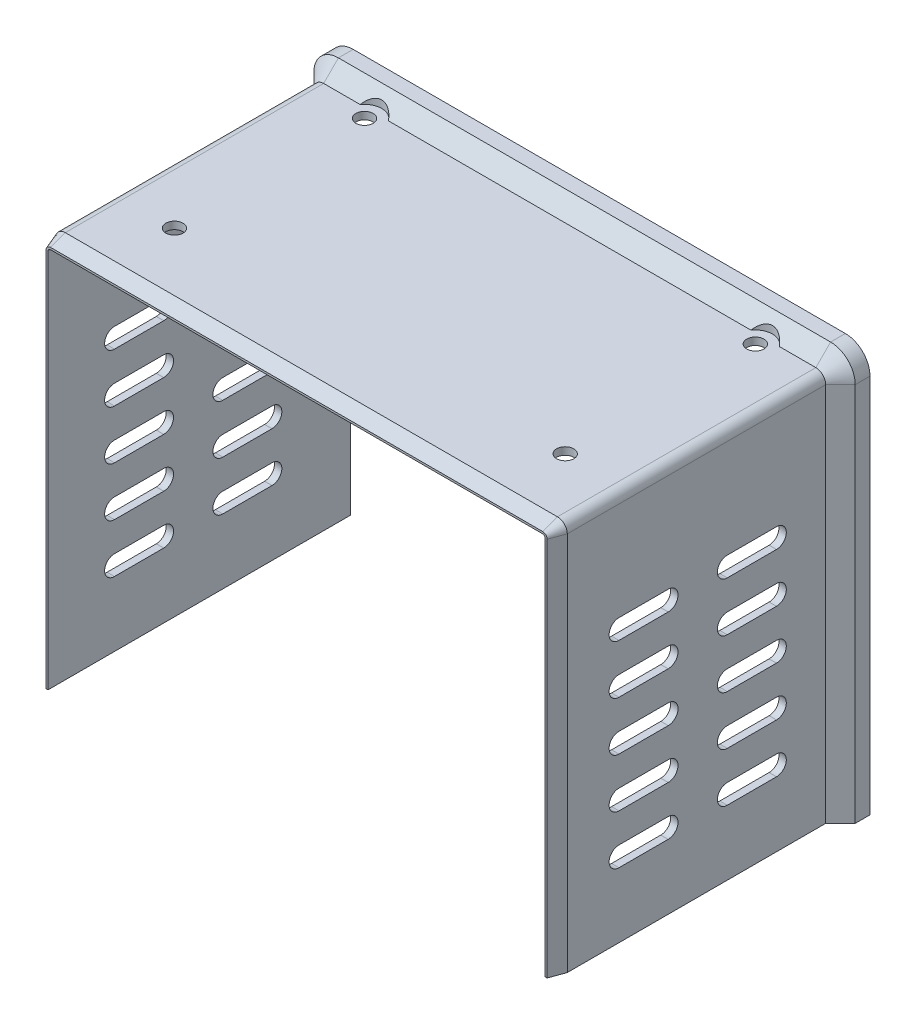
SolidWorks part; units mm, degrees
ref_plane "Front Plane" through (0, 0, 0) normal (0, 0, 1) x (1, 0, 0)
ref_plane "Top Plane" through (0, 0, 0) normal (0, 1, 0) x (1, 0, 0)
ref_plane "Right Plane" through (0, 0, 0) normal (1, 0, 0) x (0, 0, -1)
sketch "Sketch3" plane through (0, 0, 389.6201) normal (0, 0, 1) x (1, 0, 0)
  line L0 (-161.2108, -568.2989) -> (-161.2108, -472.2989) construction
  line L1 (-161.2108, -470.0989) -> (-61.2108, -470.0989)
  line L2 (-161.7108, -470.5989) -> (-161.7108, -544.9977)
  line L4 (-60.7108, -470.5989) -> (-60.7108, -547.7989)
  line L5 (-61.2108, -472.2989) -> (-61.2108, -568.2989) construction
  line L6 (-159.2108, -470.2989) -> (-118.3071, -470.2989) construction
  line L7 (-163.2108, -470.5989) -> (-163.2108, -547.7989)
  line L8 (-161.2108, -468.5989) -> (-61.2108, -468.5989)
  line L9 (-59.2108, -470.5989) -> (-59.2108, -547.7989)
  line L10 (-163.2108, -547.7989) -> (-161.7108, -547.7989)
  line L11 (-59.2108, -547.7989) -> (-60.7108, -547.7989)
  line L12 (-161.7108, -470.0989) -> (-60.7108, -470.0989) construction
  line L13 (-161.7108, -470.0989) -> (-161.7108, -547.7989) construction
  line L14 (-163.2108, -468.5989) -> (-59.2108, -468.5989) construction
  line L15 (-163.2108, -468.5989) -> (-163.2108, -547.7989) construction
  line L16 (-59.2108, -468.5989) -> (-59.2108, -547.7989) construction
  line L17 (-60.7108, -470.0989) -> (-60.7108, -547.7989) construction
  line L18 (-161.7108, -544.9977) -> (-161.7108, -547.7989)
  line L19 (-175.2108, -548.2989) -> (-161.8182, -548.2989) construction
  line L20 (-60.2182, -548.2989) -> (-47.2108, -548.2989) construction
  arc A1 (-161.2108, -470.0989) -> (-161.7108, -470.5989) centre (-161.2108, -470.5989) ccw
  arc A3 (-161.2108, -468.5989) -> (-163.2108, -470.5989) centre (-161.2108, -470.5989) ccw
  arc A4 (-59.2108, -470.5989) -> (-61.2108, -468.5989) centre (-61.2108, -470.5989) ccw
  arc A5 (-60.7108, -470.5989) -> (-61.2108, -470.0989) centre (-61.2108, -470.5989) ccw
  dimension "D5" = 0.5
  dimension "D6" = 2
  dimension "D7" = 2
  dimension "D8" = 0.5
  dimension "D1" = 0.5
  dimension "D2" = 0.5
  dimension "D3" = 0.2
  dimension "D9" = 0.5
  dimension "D10" = 0.5
  dimension "D4" = 1.5
extrude "Boss-Extrude1" add sketch "Sketch3" along normal blind 61.5
chamfer "Chamfer1" distance 3 angle 20 5 edges at (-59.2108, -509.1989, 451.1201) (-163.2108, -509.1989, 451.1201) (-59.7966, -469.1847, 451.1201) (-162.6251, -469.1847, 451.1201) (-111.2108, -468.5989, 451.1201) first distance on face at (-59.2108, -509.1989, 420.3701) first distance on face at (-163.2108, -509.1989, 420.3701) first distance on face at (-60.0037, -469.3918, 420.3701) first distance on face at (-162.418, -469.3918, 420.3701) first distance on face at (-111.2108, -468.5989, 420.3701)
sketch "Sketch4" plane through (0, -468.5989, 0) normal (0, 1, 0) x (1, 0, 0)
  line L0 (-163.2108, -448.1201) -> (-163.2108, -389.6201) construction
  line L1 (-61.2108, -389.6201) -> (-161.2108, -389.6201) construction
  line L2 (-111.2108, -389.6201) -> (-111.2108, -452.2414) construction
  line L3 (-61.2108, -452.2414) -> (-161.2108, -452.2414) construction
  line L5 (-59.2108, -448.1201) -> (-59.2108, -389.6201) construction
  circle A0 centre (-150.9108, -397.6201) radius 1.75
  circle A1 centre (-71.5108, -397.6201) radius 1.75
  circle A2 centre (-71.5108, -436.2414) radius 1.75
  circle A3 centre (-150.9108, -436.2414) radius 1.75
  dimension "D1" = 12.3
  dimension "D2" = 8
  dimension "D3" = 3.5
  dimension "D5" = 16
  dimension "D6" = 12.3
  dimension "D7" = 12.3
  dimension "D4" = 16
extrude "Cut-Extrude1" cut sketch "Sketch4" against normal blind 10
sketch "Sketch5" plane through (0, 0, 389.6201) normal (0, 0, -1) x (-1, 0, 0)
  line L9 (59.3108, -547.7989) -> (59.3108, -470.5989)
  line L10 (61.2108, -468.6989) -> (161.2108, -468.6989)
  line L11 (163.1108, -470.5989) -> (163.1108, -547.7989)
  line L12 (166.2108, -470.5989) -> (166.2108, -547.7989)
  line L13 (61.2108, -465.5989) -> (161.2108, -465.5989)
  line L14 (56.2108, -547.7989) -> (56.2108, -470.5989)
  line L15 (166.2108, -470.5989) -> (166.2108, -547.7989)
  line L16 (61.2108, -465.5989) -> (161.2108, -465.5989)
  line L17 (56.2108, -547.7989) -> (56.2108, -470.5989)
  line L18 (56.2108, -547.7989) -> (59.3108, -547.7989)
  line L19 (163.1108, -547.7989) -> (166.2108, -547.7989)
  arc A6 (61.2108, -468.6989) -> (59.3108, -470.5989) centre (61.2108, -470.5989) ccw
  arc A7 (163.1108, -470.5989) -> (161.2108, -468.6989) centre (161.2108, -470.5989) ccw
  arc A8 (166.2108, -470.5989) -> (161.2108, -465.5989) centre (161.2108, -470.5989) ccw
  arc A9 (61.2108, -465.5989) -> (56.2108, -470.5989) centre (61.2108, -470.5989) ccw
  arc A10 (166.2108, -470.5989) -> (161.2108, -465.5989) centre (161.2108, -470.5989) ccw
  arc A11 (61.2108, -465.5989) -> (56.2108, -470.5989) centre (61.2108, -470.5989) ccw
  dimension "D1" = 3
  dimension "D2" = 3.1
extrude "Boss-Extrude2" add sketch "Sketch5" against normal blind 3
chamfer "Chamfer2" distance 3 angle 45 5 edges at (-163.2108, -509.1989, 392.6201) (-162.6251, -469.1847, 392.6201) (-111.2108, -468.5989, 392.6201) (-59.7966, -469.1847, 392.6201) (-59.2108, -509.1989, 392.6201)
sketch "Sketch6" plane through (-59.2108, 0, 0) normal (1, 0, 0) x (0, 0, -1)
  line L0 (-437.6201, -492.5989) -> (-427.6201, -492.5989) construction
  line L1 (-437.6201, -490.5989) -> (-427.6201, -490.5989)
  line L2 (-437.6201, -494.5989) -> (-427.6201, -494.5989)
  line L3 (-448.1201, -470.5989) -> (-448.1201, -547.7989) construction
  line L4 (-448.1201, -470.5989) -> (-395.6201, -470.5989) construction
  line L5 (-415.6201, -492.5989) -> (-405.6201, -492.5989) construction
  line L6 (-415.6201, -490.5989) -> (-405.6201, -490.5989)
  line L7 (-415.6201, -494.5989) -> (-405.6201, -494.5989)
  line L8 (-437.6201, -522.5989) -> (-427.6201, -522.5989) construction
  line L9 (-437.6201, -502.5989) -> (-427.6201, -502.5989) construction
  line L10 (-437.6201, -500.5989) -> (-427.6201, -500.5989)
  line L11 (-437.6201, -504.5989) -> (-427.6201, -504.5989)
  line L12 (-415.6201, -502.5989) -> (-405.6201, -502.5989) construction
  line L13 (-415.6201, -500.5989) -> (-405.6201, -500.5989)
  line L14 (-415.6201, -504.5989) -> (-405.6201, -504.5989)
  line L15 (-437.6201, -512.5989) -> (-427.6201, -512.5989) construction
  line L16 (-437.6201, -510.5989) -> (-427.6201, -510.5989)
  line L17 (-437.6201, -514.5989) -> (-427.6201, -514.5989)
  line L18 (-415.6201, -512.5989) -> (-405.6201, -512.5989) construction
  line L19 (-415.6201, -510.5989) -> (-405.6201, -510.5989)
  line L20 (-415.6201, -514.5989) -> (-405.6201, -514.5989)
  line L21 (-437.6201, -520.5989) -> (-427.6201, -520.5989)
  line L22 (-437.6201, -524.5989) -> (-427.6201, -524.5989)
  line L23 (-415.6201, -522.5989) -> (-405.6201, -522.5989) construction
  line L24 (-415.6201, -520.5989) -> (-405.6201, -520.5989)
  line L25 (-415.6201, -524.5989) -> (-405.6201, -524.5989)
  line L26 (-437.6201, -532.5989) -> (-427.6201, -532.5989) construction
  line L27 (-437.6201, -530.5989) -> (-427.6201, -530.5989)
  line L28 (-437.6201, -534.5989) -> (-427.6201, -534.5989)
  line L29 (-415.6201, -532.5989) -> (-405.6201, -532.5989) construction
  line L30 (-415.6201, -530.5989) -> (-405.6201, -530.5989)
  line L31 (-415.6201, -534.5989) -> (-405.6201, -534.5989)
  arc A0 (-437.6201, -490.5989) -> (-437.6201, -494.5989) centre (-437.6201, -492.5989) ccw
  arc A1 (-427.6201, -494.5989) -> (-427.6201, -490.5989) centre (-427.6201, -492.5989) ccw
  arc A2 (-415.6201, -490.5989) -> (-415.6201, -494.5989) centre (-415.6201, -492.5989) ccw
  arc A3 (-405.6201, -494.5989) -> (-405.6201, -490.5989) centre (-405.6201, -492.5989) ccw
  arc A4 (-437.6201, -500.5989) -> (-437.6201, -504.5989) centre (-437.6201, -502.5989) ccw
  arc A5 (-427.6201, -504.5989) -> (-427.6201, -500.5989) centre (-427.6201, -502.5989) ccw
  arc A6 (-415.6201, -500.5989) -> (-415.6201, -504.5989) centre (-415.6201, -502.5989) ccw
  arc A7 (-405.6201, -504.5989) -> (-405.6201, -500.5989) centre (-405.6201, -502.5989) ccw
  arc A8 (-437.6201, -510.5989) -> (-437.6201, -514.5989) centre (-437.6201, -512.5989) ccw
  arc A9 (-427.6201, -514.5989) -> (-427.6201, -510.5989) centre (-427.6201, -512.5989) ccw
  arc A10 (-415.6201, -510.5989) -> (-415.6201, -514.5989) centre (-415.6201, -512.5989) ccw
  arc A11 (-405.6201, -514.5989) -> (-405.6201, -510.5989) centre (-405.6201, -512.5989) ccw
  arc A12 (-437.6201, -520.5989) -> (-437.6201, -524.5989) centre (-437.6201, -522.5989) ccw
  arc A13 (-427.6201, -524.5989) -> (-427.6201, -520.5989) centre (-427.6201, -522.5989) ccw
  arc A14 (-415.6201, -520.5989) -> (-415.6201, -524.5989) centre (-415.6201, -522.5989) ccw
  arc A15 (-405.6201, -524.5989) -> (-405.6201, -520.5989) centre (-405.6201, -522.5989) ccw
  arc A16 (-437.6201, -530.5989) -> (-437.6201, -534.5989) centre (-437.6201, -532.5989) ccw
  arc A17 (-427.6201, -534.5989) -> (-427.6201, -530.5989) centre (-427.6201, -532.5989) ccw
  arc A18 (-415.6201, -530.5989) -> (-415.6201, -534.5989) centre (-415.6201, -532.5989) ccw
  arc A19 (-405.6201, -534.5989) -> (-405.6201, -530.5989) centre (-405.6201, -532.5989) ccw
  point P2 (-432.6201, -492.5989)
  point P14 (-410.6201, -492.5989)
  point P22 (-432.6201, -502.5989)
  point P29 (-410.6201, -502.5989)
  point P36 (-432.6201, -512.5989)
  point P43 (-410.6201, -512.5989)
  point P48 (-432.6201, -522.5989)
  point P55 (-410.6201, -522.5989)
  point P62 (-432.6201, -532.5989)
  point P69 (-410.6201, -532.5989)
  dimension "D1" = 2
  dimension "D2" = 10
  dimension "D3" = 10.5
  dimension "D4" = 20
  dimension "D6" = 5
  dimension "D5" = 2
extrude "Cut-Extrude2" cut sketch "Sketch6" against normal blind 145
sketch "Sketch7" plane through (0, -468.5989, 0) normal (0, 1, 0) x (1, 0, 0)
  circle A0 centre (-150.9108, -397.6201) radius 3.5
  circle A1 centre (-71.5108, -397.6201) radius 3.5
extrude "Cut-Extrude3" cut sketch "Sketch7" along normal blind 10
